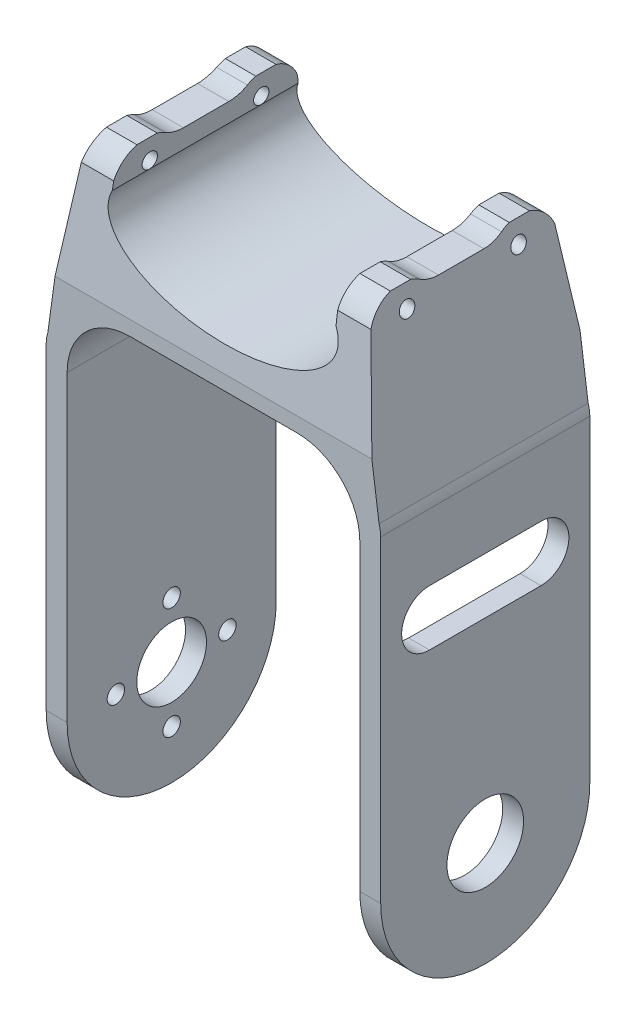
SolidWorks part; units mm, degrees
note: The reader was unsure of these and kept them because the rebuilt part matched: shared geometry of "Эскиз3<4>".
ref_plane "Спереди" through (0, 0, 0) normal (0, 0, 1) x (1, 0, 0)
ref_plane "Сверху" through (0, 0, 0) normal (0, 1, 0) x (1, 0, 0)
ref_plane "Справа" through (0, 0, 0) normal (1, 0, 0) x (0, 0, -1)
sketch "Эскиз1" plane through (0, 0, 0) normal (0, 0, 1) x (1, 0, 0)
  line L0 (-0.5529, 19.3299) -> (-0.5529, 52.5803) construction
  line L1 (-0.5529, 19.3299) -> (-0.5529, -49.2992) construction
  line L2 (23.2129, 9.6952) -> (19.8144, 34.416)
  line L3 (-21.5529, -52.3669) -> (-24.5529, -52.3669)
  line L4 (-16.7372, 30.3068) -> (-16.5529, 34.416)
  line L5 (-21.5529, -52.3669) -> (-21.5529, 5.955)
  line L6 (-24.5529, -52.3669) -> (-24.5529, 8.1828)
  line L7 (-20.9202, 34.416) -> (-16.5529, 34.416)
  line L8 (-24.3187, 9.6952) -> (-20.9202, 34.416)
  line L15 (-0.5529, 46.1948) -> (-0.6138, 46.2579)
  line L16 (-21.5529, 5.955) -> (-21.5529, 6.1114)
  line L17 (11.4471, 15.1114) -> (-12.5529, 15.1114)
  line L21 (15.4471, 29.6011) -> (15.4471, 34.416)
  line L24 (20.4471, 5.955) -> (20.4471, 6.1114)
  line L25 (-0.5529, 46.1948) -> (-0.492, 46.2579)
  line L34 (23.4471, -52.3669) -> (23.4471, 8.1828)
  line L35 (20.4471, -52.3669) -> (20.4471, 5.955)
  line L36 (19.8144, 34.416) -> (15.4471, 34.416)
  line L37 (20.4471, -52.3669) -> (23.4471, -52.3669)
  arc A0 (-12.5529, 15.1114) -> (-21.5529, 6.1114) centre (-12.5529, 6.1114) ccw
  arc A1 (11.4471, 15.1114) -> (20.4471, 6.1114) centre (11.4471, 6.1114) cw
  arc A2 (23.4471, 8.1828) -> (23.2129, 9.6952) centre (18.4471, 8.1828) ccw
  arc A19 (-24.3187, 9.6952) -> (-24.5529, 8.1828) centre (-19.5529, 8.1828) ccw
  ellipse E0 centre (-0.5529, 28.1714) end of major axis (15.9987, 27.4808) minor radius 7.6153 (-16.7372, 30.3068) -> (15.4471, 29.6011) ccw
  point P40 (-0.5529, 15.1114)
  point P54 (23.4471, 8.9571)
  point P105 (-24.5529, 8.9571)
  dimension "D2" = 9
  dimension "D3" = 5
  dimension "D5" = 21
  dimension "D10" = 86.7828
  dimension "D1" = 62.0621
  dimension "D4" = 16
  dimension "D6" = 24
  dimension "D7" = 187.828
  dimension "D8" = 9.1563
  dimension "D13" = 34.416
  dimension "D16" = 0.5529
  dimension "D17" = 52.3669
  dimension "D18" = 23.7658
  dimension "D29" = 5.4606
extrude "Бобышка-Вытянуть1" add sketch "Эскиз1" along normal blind 30
sketch "Эскиз2" plane through (23.4471, 0, 0) normal (1, 0, 0) x (0, 0, -1)
  line L0 (-15, -52.3669) -> (-15, 46.6662) construction
  line L1 (-30, -52.3669) -> (0, -52.3669) construction
  line L2 (-6.4725, 34.6331) -> (-23.5275, 34.6331)
  line L3 (-30.3535, 34.9521) -> (-23.5275, 34.6331)
  line L4 (0.5091, 34.9531) -> (-6.4725, 34.6331)
  line L5 (0.5091, 14.4531) -> (0.5091, 34.9531)
  line L6 (-1.8152, 31.4521) -> (0.5091, 14.4531)
  line L7 (-11.7404, 33.1331) -> (-18.2596, 33.1331)
  line L9 (-30.3535, 14.4521) -> (-30.3535, 34.9521)
  line L11 (-23.5275, 34.6331) -> (-15, 34.6331)
  line L14 (-30.3535, 14.4521) -> (-28.1848, 31.4521)
  arc A0 (-23.5275, 34.6331) -> (-28.1848, 31.4521) centre (-23.5275, 29.6331) ccw
  arc A1 (-20.8935, 33.8831) -> (-28.1848, 31.4521) centre (-23.5275, 29.6331) ccw
  arc A2 (-18.2596, 33.1331) -> (-20.8935, 33.8831) centre (-18.2596, 38.1331) cw
  arc A3 (-11.7404, 33.1331) -> (-9.1065, 33.8831) centre (-11.7404, 38.1331) ccw
  arc A4 (-9.1065, 33.8831) -> (-1.8152, 31.4521) centre (-6.4725, 29.6331) cw
  arc A5 (-6.4725, 34.6331) -> (-1.8152, 31.4521) centre (-6.4725, 29.6331) cw
  point P29 (-15, 33.1331)
  point P30 (-15, 34.6331)
  dimension "D3" = 20.5
  dimension "D5" = 5
  dimension "D6" = 5
  dimension "D1" = 7.27
  dimension "D2" = 87
  dimension "D4" = 20.5
  dimension "D7" = 1.5
  dimension "D8" = 6.9817
  dimension "D9" = 26.3696
  dimension "D10" = 66.819
  dimension "D11" = 66.82
  dimension "D12" = 17
sketch "Эскиз3" plane through (23.4471, 0, 0) normal (1, 0, 0) x (0, 0, -1)
  line L0 (-15, -52.3669) -> (-15, 46.9077) construction
  line L1 (-30, -52.3669) -> (0, -52.3669) construction
  line L2 (-30, -37.3669) -> (0, -37.3669) construction
  circle A0 centre (-23, 31.416) radius 1.1
  circle A1 centre (-7, 31.416) radius 1.1
  circle A2 centre (-15, -37.3669) radius 5
  arc A3 (-30, -37.3669) -> (0, -37.3669) centre (-15, -37.3669) ccw
  dimension "D1" = 8
  dimension "D2" = 2.2
  dimension "D3" = 2.2
  dimension "D5" = 30
  dimension "D4" = 31.416
extrude "Вырез-Вытянуть5" cut sketch "Эскиз3" against normal blind 56 contours A2 | A3 L2 A0 | A3 A0 L0
extrude "Вырез-Вытянуть12" cut sketch "Эскиз2" against normal blind 51 contours A0 L3 L9 L14 | L7 L0 L2 A1 A2 | L0 L7 A3 A4 L2 | L4 A4 L6 L5
extrude "Вырез-Вытянуть7" cut sketch "Эскиз3<4>" against normal blind 56 contours A0 | A1
sketch "Эскиз3<4>" plane through (23.4471, 0, 0) normal (1, 0, 0) x (0, 0, -1) same geometry as "Эскиз3"
sketch "Эскиз5" plane through (23.4471, 0, 0) normal (1, 0, 0) x (0, 0, -1)
  line L0 (-15, -37.4383) -> (-15, 43.4678) construction
  line L1 (-15, -37.3669) -> (-15, -9.3669)
  line L2 (-15, -9.3669) -> (-15, -1.3669)
  line L3 (-15, -1.3669) -> (-23, -1.3669)
  line L5 (-23, -9.3669) -> (-7, -9.3669)
  line L7 (-7, -1.3669) -> (-15, -1.3669)
  circle A1 centre (-15, -37.3669) radius 5.5
  arc A2 (-23, -9.3669) -> (-23, -1.3669) centre (-23, -5.3669) cw
  arc A3 (-7, -9.3669) -> (-7, -1.3669) centre (-7, -5.3669) ccw
  dimension "D1" = 11
  dimension "D4" = 8
  dimension "D2" = 28
  dimension "D3" = 8
sketch "Эскиз6" plane through (-24.5529, 0, 0) normal (-1, 0, 0) x (0, 0, 1)
  line L0 (15, -37.3669) -> (15, -8.1968) construction
  line L1 (0, -37.3669) -> (30, -37.3669) construction
  circle A0 centre (15, -37.3669) radius 8
  circle A2 centre (15, -29.3669) radius 1.25
  circle A3 centre (7, -37.3669) radius 1.25
  circle A4 centre (23, -37.3669) radius 1.25
  circle A5 centre (15, -45.3669) radius 1.25
  dimension "D1" = 2.5
  dimension "D2" = 16
  dimension "D3" = 2.5
  dimension "D4" = 2.5
  dimension "D5" = 2.5
extrude "Вырез-Вытянуть9" cut sketch "Эскиз6" against normal blind 22 contours A2 | A4 | A5 | A3
extrude "Вырез-Вытянуть13" cut sketch "Эскиз5" against normal blind 10 contours L3 A2 L5 A3 L7 | A1
